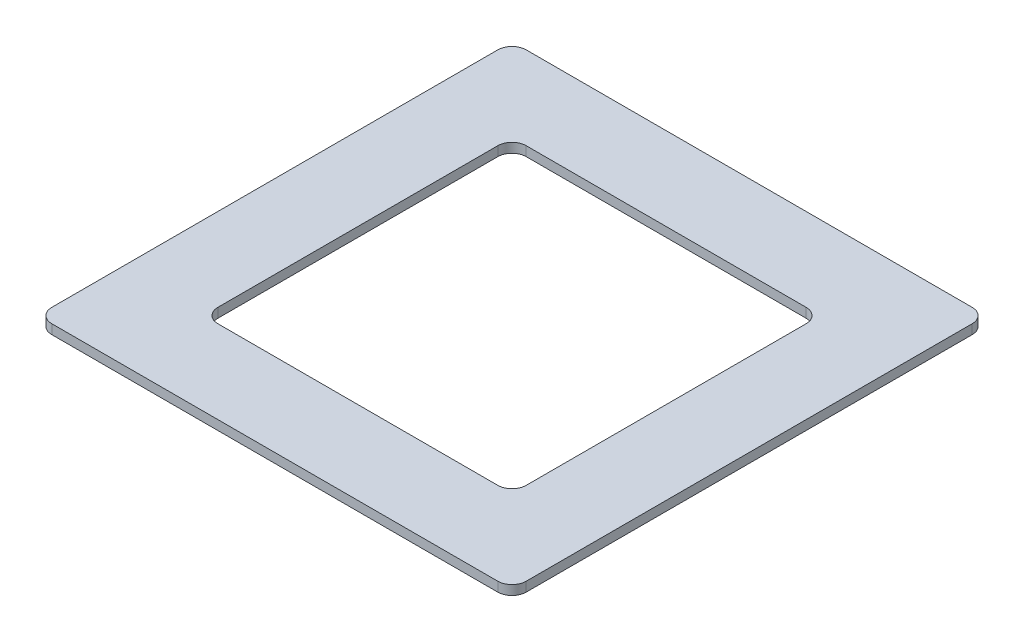
SolidWorks part; units mm, degrees
ref_plane "前视基准面" through (0, 0, 0) normal (0, 0, 1) x (1, 0, 0)
ref_plane "上视基准面" through (0, 0, 0) normal (0, 1, 0) x (1, 0, 0)
ref_plane "右视基准面" through (0, 0, 0) normal (1, 0, 0) x (0, 0, -1)
sketch "草图1" plane through (0, 0, 0) normal (0, 1, 0) x (1, 0, 0)
  line L0 (20.5, -17.5) -> (79.5, -17.5)
  line L1 (3, 0) -> (97, 0)
  line L2 (0, -3) -> (0, -97)
  line L3 (3, -100) -> (97, -100)
  line L4 (100, -3) -> (100, -97)
  line L5 (82.5, -20.5) -> (82.5, -79.5)
  line L6 (20.5, -82.5) -> (79.5, -82.5)
  line L7 (17.5, -20.5) -> (17.5, -79.5)
  line L8 (17.5, -17.5) -> (17.5, -82.5) construction
  line L9 (17.5, -82.5) -> (82.5, -82.5) construction
  line L10 (17.5, -17.5) -> (82.5, -17.5) construction
  line L11 (82.5, -17.5) -> (82.5, -82.5) construction
  arc A0 (0, -3) -> (3, 0) centre (3, -3) cw
  arc A1 (0, -97) -> (3, -100) centre (3, -97) ccw
  arc A2 (97, -100) -> (100, -97) centre (97, -97) ccw
  arc A3 (97, 0) -> (100, -3) centre (97, -3) cw
  arc A4 (82.5, -79.5) -> (79.5, -82.5) centre (79.5, -79.5) cw
  arc A6 (20.5, -17.5) -> (17.5, -20.5) centre (20.5, -20.5) ccw
  arc A7 (79.5, -17.5) -> (82.5, -20.5) centre (79.5, -20.5) cw
  arc A8 (17.5, -79.5) -> (20.5, -82.5) centre (20.5, -79.5) ccw
  arc A9 (17.5, -82.5) -> (17.5, -82.5) centre (17.5, -82.5) ccw construction
  arc A10 (17.5, -17.5) -> (17.5, -17.5) centre (17.5, -17.5) cw construction
  arc A11 (82.5, -17.5) -> (82.5, -17.5) centre (82.5, -17.5) cw construction
  arc A12 (82.5, -82.5) -> (82.5, -82.5) centre (82.5, -82.5) ccw construction
  point P7 (0, 0)
  point P10 (0, -100)
  point P15 (100, 0)
  dimension "D3" = 3
  dimension "D4" = 3
  dimension "D5" = 17.5
  dimension "D6" = 3
  dimension "D7" = 3
  dimension "D1" = 100
  dimension "D2" = 100
extrude "凸台-拉伸1" add sketch "草图1" along normal blind 2
ref_axis "基准轴1" through (0, 0, 0) along (0, 1, 0)
